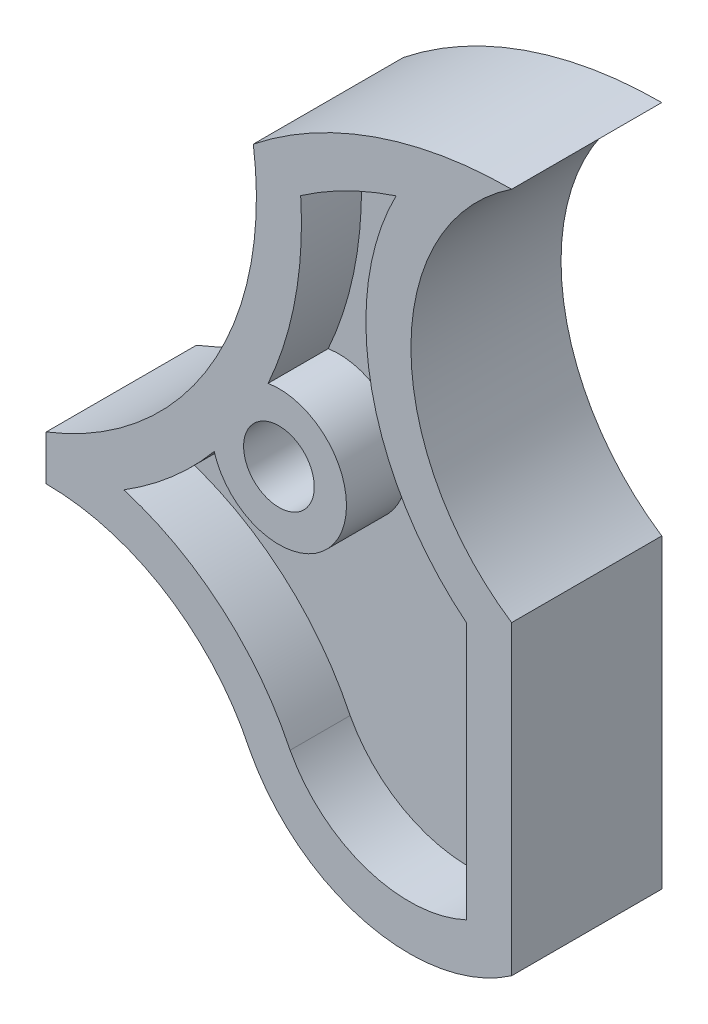
SolidWorks part; units mm, degrees
ref_plane "Alzado" through (0, 0, 0) normal (0, 0, 1) x (1, 0, 0)
ref_plane "Planta" through (0, 0, 0) normal (0, 1, 0) x (1, 0, 0)
ref_plane "Vista lateral" through (0, 0, 0) normal (1, 0, 0) x (0, 0, -1)
sketch "Croquis1" plane through (0, 0, 0) normal (0, 0, 1) x (1, 0, 0)
  line L1 (-15.5, -23.75) -> (15.5, -23.75)
  line L2 (-15.5, -23.75) -> (-15.5, 23.75)
  line L3 (-15.5, 23.75) -> (15.5, 23.75)
  line L4 (15.5, -23.75) -> (15.5, 23.75)
  line L5 (-15.5, -23.75) -> (15.5, 23.75) construction
  line L6 (-15.5, 23.75) -> (15.5, -23.75) construction
  circle A0 centre (0, 0) radius 1.5
  dimension "D1" = 3
  dimension "D2" = 47.5
  dimension "D3" = 31
extrude "Saliente-Extruir1" add sketch "Croquis1" along normal mid plane 10
sketch "Croquis2" plane through (0, 0, 5) normal (0, 0, 1) x (1, 0, 0)
  line L0 (-15.5, -8.75) -> (63.2071, -8.75) construction
  line L4 (15.5, -23.75) -> (15.5, 23.75)
  line L5 (15.5, 23.75) -> (-15.5, 23.75)
  line L6 (-15.5, 23.75) -> (-15.5, -23.75)
  line L7 (-15.5, -23.75) -> (15.5, -23.75)
  line L8 (15.5, -23.75) -> (15.5, 23.75)
  line L9 (15.5, 23.75) -> (-15.5, 23.75)
  line L10 (-15.5, 23.75) -> (-15.5, -23.75)
  line L11 (-15.5, -23.75) -> (15.5, -23.75)
  circle A0 centre (-15.5, -23.75) radius 15
  arc A1 (-1.9396, -17.3378) -> (15.5, -21.6236) centre (8.68, -11.75) ccw
  arc A2 (15.5, 23.75) -> (15.5, -1.25) centre (23.7916, 11.25) ccw
  arc A3 (-15.5, -5.75) -> (-1.7063, 17.75) centre (-23.5, 14.7439) ccw
  arc A4 (-1.7063, 17.75) -> (15.5, 23.75) centre (15.5, -3.9215) cw
  line M5 (15.5, -23.75) -> (15.5, 23.75)
  line M6 (15.5, 23.75) -> (-15.5, 23.75)
  line M7 (-15.5, 23.75) -> (-15.5, -23.75)
  line M8 (-15.5, -23.75) -> (15.5, -23.75)
  dimension "D2" = 30
  dimension "D3" = 25
  dimension "D4" = 15
  dimension "D5" = 12
  dimension "D9" = 22
  dimension "D6" = 6.82
  dimension "D7" = 3
  dimension "D8" = 6
  dimension "D10" = 8
  dimension "D1" = 0
extrude "Cortar-Extruir1" cut sketch "Croquis2" against normal blind 10 contours A0 L10 M8 | A1 A0 L11 | A1 M8 M5 | A3 A4 M6 M7 | A2 M5 region at (13.8267, -23.1231, 5) region at (1.4464, -22.26, 5) region at (12.7575, 11.25, 5) region at (-9.1338, -17.3838, 5) region at (-8.2316, 12.2777, 5)
sketch "Croquis4" plane through (0, 0, 5) normal (0, 0, 1) x (1, 0, 0)
  line L2 (15.5, -21.6236) -> (15.5, -1.25)
  line L3 (-15.5, -5.75) -> (-15.5, -8.75)
  line L4 (15.5, -21.6236) -> (15.5, -1.25)
  line L5 (-15.5, -5.75) -> (-15.5, -8.75)
  line L8 (12.5, -19.8991) -> (12.5, -2.7679)
  line L9 (12.5, -19.8991) -> (12.5, -2.7679)
  arc A5 (-1.9396, -17.3378) -> (15.5, -21.6236) centre (8.68, -11.75) ccw
  arc A6 (15.5, 23.75) -> (15.5, -1.25) centre (23.7916, 11.25) ccw
  arc A7 (15.5, 23.75) -> (-1.7063, 17.75) centre (15.5, -3.9215) ccw
  arc A8 (-15.5, -5.75) -> (-1.7063, 17.75) centre (-23.5, 14.7439) ccw
  arc A9 (-1.9396, -17.3378) -> (-15.5, -8.75) centre (-15.5, -23.75) ccw
  arc A10 (-1.9396, -17.3378) -> (15.5, -21.6236) centre (8.68, -11.75) ccw
  arc A11 (15.5, 23.75) -> (15.5, -1.25) centre (23.7916, 11.25) ccw
  arc A12 (15.5, 23.75) -> (-1.7063, 17.75) centre (15.5, -3.9215) ccw
  arc A13 (-15.5, -5.75) -> (-1.7063, 17.75) centre (-23.5, 14.7439) ccw
  arc A14 (-1.9396, -17.3378) -> (-15.5, -8.75) centre (-15.5, -23.75) ccw
  arc A20 (0.7418, -15.9908) -> (12.5, -19.8991) centre (8.68, -11.75) ccw
  arc A21 (7.8032, 19.5187) -> (12.5, -2.7679) centre (23.7916, 11.25) ccw
  arc A22 (7.8032, 19.5187) -> (1.4479, 16.3571) centre (15.5, -3.9215) ccw
  arc A23 (-10.3328, -6.5076) -> (1.4479, 16.3571) centre (-23.5, 14.7439) ccw
  arc A24 (0.7418, -15.9908) -> (-10.3328, -6.5076) centre (-15.5, -23.75) ccw
  arc A25 (0.7418, -15.9908) -> (12.5, -19.8991) centre (8.68, -11.75) ccw
  arc A26 (7.8032, 19.5187) -> (12.5, -2.7679) centre (23.7916, 11.25) ccw
  arc A27 (7.8032, 19.5187) -> (1.4479, 16.3571) centre (15.5, -3.9215) ccw
  arc A28 (-10.3328, -6.5076) -> (1.4479, 16.3571) centre (-23.5, 14.7439) ccw
  arc A29 (0.7418, -15.9908) -> (-10.3328, -6.5076) centre (-15.5, -23.75) ccw
  circle M21 centre (0, 0) radius 1.5
  dimension "D1" = 0
  dimension "D2" = 3
extrude "Cortar-Extruir2" cut sketch "Croquis4" against normal blind 4 contours A29 A25 L9 A26 A27 A28 M21 region at (4.0436, -4.6033, 5)
mirror "Simetría1" about plane through (0, 0, 0) normal (0, 0, 1) of "Cortar-Extruir2"
sketch "Croquis5" plane through (0, 0, 1) normal (0, 0, 1) x (1, 0, 0)
  circle A0 centre (0, 0) radius 1.5 construction
  circle A1 centre (0, 0) radius 1.5
  circle A2 centre (0, 0) radius 2.355
  circle A3 centre (0, 0) radius 4.5
  arc M6 (1.4479, 16.3571) -> (-10.3328, -6.5076) centre (-23.5, 14.7439) cw
  dimension "D1" = 4.71
  dimension "D2" = 9
extrude "Saliente-Extruir2" add sketch "Croquis5" along normal up to surface (4 mm away) and the other way up to surface (6 mm away) contours A3 A2 M6 region at (0.6302, -4.3284, 1) up to face at (1.285, -2.3005, 5) other way up to face at (3.9937, -2.1171, -5)
